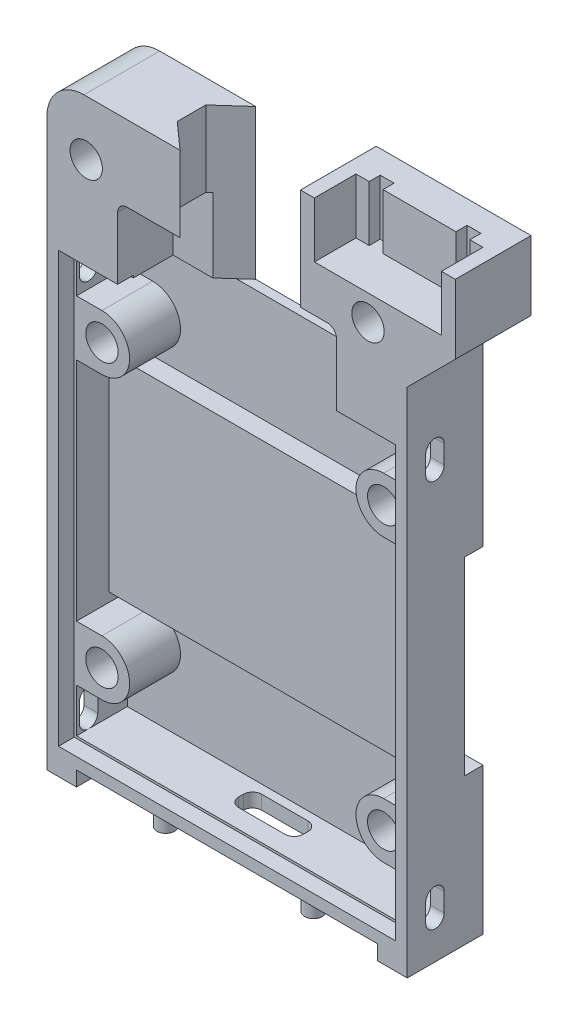
SolidWorks part; units mm, degrees
ref_plane "Front Plane" through (0, 0, 0) normal (0, 0, 1) x (1, 0, 0)
ref_plane "Top Plane" through (0, 0, 0) normal (0, 1, 0) x (1, 0, 0)
ref_plane "Right Plane" through (0, 0, 0) normal (1, 0, 0) x (0, 0, -1)
sketch "Sketch1" plane through (0, 0, 0) normal (0, 0, 1) x (1, 0, 0)
  line L0 (15.25, -20.35) -> (18, -20.35)
  line L1 (-19.5, -32.6) -> (19.5, -32.6)
  line L2 (-19.5, -32.6) -> (-19.5, 31.1)
  line L3 (-19.5, 31.1) -> (19.5, 31.1)
  line L4 (19.5, -32.6) -> (19.5, 31.1)
  line L5 (-15.25, -20.35) -> (-18, -20.35)
  line L6 (15.25, -26.35) -> (18, -26.35)
  line L7 (6.95, 31.1) -> (-15.5, 31.1) construction
  line L8 (-18, -31.1) -> (-18, 29.6)
  line L9 (-18, 29.6) -> (18, 29.6)
  line L10 (18, -31.1) -> (18, 29.6)
  line L11 (-18, -31.1) -> (18, -31.1)
  line L12 (-18, 14.9) -> (18, 14.9)
  line L13 (7.85, 14.9) -> (-4.95, 14.9) construction
  line L14 (-15.25, 4.15) -> (-18, 4.15)
  line L15 (-15.25, 10.15) -> (-18, 10.15)
  line L16 (15.25, 10.15) -> (18, 10.15)
  line L17 (15.25, 4.15) -> (18, 4.15)
  line L18 (-15.25, -26.35) -> (-18, -26.35)
  line L19 (19.5, -34.2) -> (19.5, -18.35) construction
  line L20 (-19.5, -34.2) -> (-19.5, -18.35) construction
  line L21 (15.3, -32.6) -> (-15.3, -32.6) construction
  line L22 (0, 31.1) -> (0, -32.6) construction
  line L23 (9.45, 26.9) -> (24.7, 26.9)
  line L24 (9.45, 26.9) -> (9.45, 33.9)
  line L25 (9.45, 33.9) -> (24.7, 33.9)
  line L26 (24.7, 26.9) -> (24.7, 33.9)
  line L27 (18, 29.6) -> (19.5, 31.1) construction
  line L28 (18.75, 30.35) -> (0, 30.35) construction
  line L29 (9.45, 26.9) -> (7.95, 26.9) construction
  line L30 (-7.95, 31.1) -> (7.95, 31.1)
  line L31 (-7.95, 31.1) -> (-7.95, 29.6)
  line L32 (-7.95, 29.6) -> (7.95, 29.6)
  line L33 (7.95, 31.1) -> (7.95, 29.6)
  line L34 (-7.95, 31.1) -> (7.95, 29.6) construction
  line L35 (-7.95, 29.6) -> (7.95, 31.1) construction
  line L36 (7.95, 26.9) -> (7.95, 29.6) construction
  line L37 (18, 29.6) -> (19.5, 29.6) construction
  line L38 (24.7, 26.4) -> (19.5, 21.2)
  line L39 (9.45, 33.9) -> (7.95, 33.9)
  line L40 (23.2, 33.9) -> (23.2, 26.9)
  line L41 (7.95, 33.9) -> (7.95, 31.1)
  line L42 (24.7, 30.4) -> (23.2, 30.4) construction
  line L43 (24.7, 26.9) -> (19.5, 26.9)
  line L44 (24.7, 26.9) -> (24.7, 26.4)
  line L45 (24.7, 26.4) -> (19.5, 26.4)
  line L46 (19.5, 26.9) -> (19.5, 26.4)
  arc A1 (-15.5, 31.1) -> (-19.5, 27.1) centre (-15.5, 27.1) ccw construction
  arc A3 (-15.5, 31.1) -> (-19.5, 27.1) centre (-15.5, 27.1) ccw
  arc A4 (-15.5, 29.6) -> (-18, 27.1) centre (-15.5, 27.1) ccw
  circle A6 centre (-15.25, -23.35) radius 1.75
  circle A7 centre (15.25, -23.35) radius 1.75
  circle A8 centre (-15.25, 7.15) radius 1.75
  circle A9 centre (15.25, 7.15) radius 1.75
  circle A10 centre (15.25, 25.15) radius 1.75
  circle A11 centre (-15.25, 25.15) radius 1.75
  circle A12 centre (-15.25, -23.35) radius 3
  circle A13 centre (15.25, -23.35) radius 3
  circle A14 centre (15.25, 7.15) radius 3
  circle A15 centre (-15.25, 7.15) radius 3
  dimension "D2" = 1.5
  dimension "D4" = 6
  dimension "D3" = 3.5
  dimension "D5" = 13.75
  dimension "D6" = 15.9
  dimension "D7" = 7
  dimension "D8" = 45
  dimension "D9" = 0.5
  dimension "D1" = 1.5
extrude "Base shape" add sketch "Sketch1" along normal up to surface (8.2 mm away) contours L3 A3 L2 L1 L4 A15 L8 L9 L10 A14 A13 L11 A12 | A15 L15 L8 | A15 L8 L14 | A12 L5 L8 | A12 L8 L18 | A13 L10 L0 | A13 L6 L10 | A14 L10 L16 | A14 L17 L10 | L9 A4 L8 L12 L10 A11 A10 | A4 L9 L8 | L10 A13 | L10 A13 A7 | A12 L8 A6 | L8 A12 | A15 L8 A8 | L8 A15 | L10 A14 | L10 A14 A9 | L33 L3 L31 L9 | L3 L33 L9 L24 | L24 L9 L10 L23 L4 L3 | L24 L23 L10 L9 | L23 L26 L25 L24 L3 L4 | L23 L4 | L3 L24 | L25 L40 L23 L26 | L38 L45 L4 region at (16.8481, -20.9099, 0) region at (17.3601, -20.8437, 0) region at (18.7469, -8.1, 0) region at (17.3601, -25.8563, 0) region at (18.1004, -23.35, 0) region at (17.3601, 4.6437, 0) region at (16.8481, 4.7099, 0) region at (18.1004, 7.15, 0) region at (17.3601, 9.6563, 0) region at (-17.3601, -25.8563, 0) region at (-0.6044, 21.831, 0) region at (-18.1004, -23.35, 0) region at (-17.9169, -23.35, 0) region at (13.725, 28.25, 0) region at (15.3803, 29.9053, 0) region at (-17.3601, -20.8437, 0) region at (22.1, 26.65, 0) region at (17.77, 31.4935, 0) region at (-17.3601, 9.6563, 0) region at (-17.4416, 29.0416, 0) region at (8.7, 30.35, 0) region at (21.2333, 24.6667, 0) region at (23.95, 30.4, 0) region at (-16.8481, 9.5901, 0) region at (-18.1004, 7.15, 0) region at (-17.3601, 4.6437, 0) region at (0, 30.35, 0) region at (8.7, 32.5, 0)
sketch "Sketch3" plane through (19.5, 0, 0) normal (1, 0, 0) x (0, 0, -1)
  line L1 (0, -18.35) -> (-2, -18.35)
  line L2 (0, -18.35) -> (0, 2.15)
  line L3 (0, 2.15) -> (-2, 2.15)
  line L4 (-2, -18.35) -> (-2, 2.15)
  line L5 (0, -18.35) -> (2, -18.35) construction
  line L6 (0, 2.15) -> (2, 2.15) construction
  line L7 (0, -32.6) -> (0, 21.2) construction
  dimension "D1" = 2
extrude "Strap cut" cut sketch "Sketch3" against normal through all
sketch "Sketch4" plane through (0, 31.1, 0) normal (0, 1, 0) x (1, 0, 0)
  line L2 (7.95, 0) -> (-5.0998, 0)
  line L4 (-15.5, 0) -> (7.95, 0) construction
  line L5 (-15.5, -8.2) -> (7.95, -8.2) construction
  line L6 (7.95, -8.2) -> (-5.0998, -8.2)
  line L12 (7.95, -8.3) -> (7.95, 0.1)
  line L13 (7.95, 0.1) -> (-4.9883, 0.1)
  line L14 (-4.9883, 0.1) -> (-7.95, -2.5553)
  line L15 (-7.95, -2.5553) -> (-7.95, -5.6447)
  line L16 (-7.95, -5.6447) -> (-4.9883, -8.3)
  line L17 (-4.9883, -8.3) -> (7.95, -8.3)
  line L18 (7.95, -8.3) -> (7.95, 0.1)
  line L19 (7.95, 0.1) -> (-4.9883, 0.1)
  line L20 (-4.9883, 0.1) -> (-7.95, -2.5553)
  line L21 (-7.95, -2.5553) -> (-7.95, -5.6447)
  line L22 (-7.95, -5.6447) -> (-4.9883, -8.3)
  line L23 (-4.9883, -8.3) -> (7.95, -8.3)
  dimension "D1" = 0.1
extrude "XT60 cut" cut sketch "Sketch4" against normal up to next contours L21 L22 L18 L20 region at (0.4142, 31.1, 4.1)
sketch "Sketch5" plane through (19.5, 0, 0) normal (1, 0, 0) x (0, 0, -1)
  line L1 (-8.2, -32.6) -> (-8.2, 21.2) construction
  line L2 (-6.2, -31.1) -> (-4.2, -31.1)
  line L3 (-6.2, -31.1) -> (-6.2, -27.1)
  line L4 (-6.2, -27.1) -> (-4.2, -27.1)
  line L5 (-4.2, -31.1) -> (-4.2, -27.1)
  line L6 (-8.2, -31.1) -> (0, -31.1) construction
  line L7 (-8.2, 14.9) -> (0, 14.9) construction
  line L8 (-6.2, 14.9) -> (-4.2, 14.9)
  line L9 (-6.2, 14.9) -> (-6.2, 10.9)
  line L10 (-6.2, 10.9) -> (-4.2, 10.9)
  line L11 (-4.2, 14.9) -> (-4.2, 10.9)
  line L14 (-5.2, -27.1) -> (-5.2, -31.1) construction
  line L15 (-5.2, 14.9) -> (-5.2, 10.9) construction
  circle A0 centre (-5.2, -28.1) radius 1
  circle A1 centre (-5.2, -30.1) radius 1
  circle A2 centre (-5.2, 13.9) radius 1
  circle A3 centre (-5.2, 11.9) radius 1
  point P20 (-5.2, -29.1)
  point P31 (-5.2, 12.9)
  dimension "D3" = 4
  dimension "D1" = 2
  dimension "D2" = 2
extrude "Power wires cut" cut sketch "Sketch5" against normal through all contours A2 | A3 | A3 A2 L9 | A3 L11 A2 | A1 | A0 | A1 L5 A0 | A1 A0 L3 region at (19.5, -30.1, 5.2) region at (19.5, -29.1, 5.9766) region at (19.5, -29.1, 4.4234) region at (19.5, -28.1, 5.2) region at (19.5, 13.9, 5.2) region at (19.5, 12.9, 5.9766) region at (19.5, 12.9, 4.4234) region at (19.5, 11.9, 5.2)
sketch "Sketch6" plane through (0, 0, 8.2) normal (0, 0, 1) x (1, 0, 0)
  line L0 (-7.85, 15.9) -> (-7.85, 21.9) construction
  line L1 (-8.85, 22.9) -> (-10.85, 22.9) construction
  line L2 (-11.85, 15.9) -> (-11.85, 21.9) construction
  line L3 (-8.85, 14.9) -> (-10.85, 14.9) construction
  line L4 (-7.85, 15.9) -> (-7.85, 21.9)
  line L5 (-8.85, 22.9) -> (-10.85, 22.9)
  line L6 (-11.85, 15.9) -> (-11.85, 21.9)
  line L7 (-8.85, 14.9) -> (-10.85, 14.9)
  line L8 (7.85, 15.9) -> (7.85, 21.9) construction
  line L9 (8.85, 22.9) -> (10.85, 22.9) construction
  line L10 (11.85, 15.9) -> (11.85, 21.9) construction
  line L11 (8.85, 14.9) -> (10.85, 14.9) construction
  line L12 (7.85, 15.9) -> (7.85, 21.9)
  line L13 (8.85, 22.9) -> (10.85, 22.9)
  line L14 (11.85, 15.9) -> (11.85, 21.9)
  line L15 (8.85, 14.9) -> (10.85, 14.9)
  line L17 (-11.85, 15.9) -> (-7.85, 15.9)
  line L18 (-11.85, 15.9) -> (-11.85, 14.9)
  line L19 (-11.85, 14.9) -> (-7.85, 14.9)
  line L20 (-7.85, 15.9) -> (-7.85, 14.9)
  line L22 (11.85, 15.9) -> (7.85, 15.9)
  line L23 (11.85, 15.9) -> (11.85, 14.9)
  line L24 (11.85, 14.9) -> (7.85, 14.9)
  line L25 (7.85, 15.9) -> (7.85, 14.9)
  line L26 (-18, 14.9) -> (-5.0998, 14.9) construction
  line L27 (11.85, 21.9) -> (7.85, 21.9)
  line L28 (11.85, 21.9) -> (11.85, 22.9)
  line L29 (11.85, 22.9) -> (7.85, 22.9)
  line L30 (7.85, 21.9) -> (7.85, 22.9)
  line L31 (-8.85, 22.9) -> (7.95, 22.9)
  line L32 (-8.85, 22.9) -> (-8.85, 14.9)
  line L33 (-8.85, 14.9) -> (7.95, 14.9)
  line L34 (7.95, 22.9) -> (7.95, 14.9)
  line L35 (7.95, 14.9) -> (18, 14.9) construction
  line L36 (7.95, 14.9) -> (7.95, 33.9) construction
  arc A0 (-8.85, 14.9) -> (-7.85, 15.9) centre (-8.85, 15.9) ccw construction
  arc A1 (-7.85, 21.9) -> (-8.85, 22.9) centre (-8.85, 21.9) ccw construction
  arc A2 (-10.85, 22.9) -> (-11.85, 21.9) centre (-10.85, 21.9) ccw construction
  arc A3 (-11.85, 15.9) -> (-10.85, 14.9) centre (-10.85, 15.9) ccw construction
  arc A4 (-8.85, 14.9) -> (-7.85, 15.9) centre (-8.85, 15.9) ccw
  arc A5 (-7.85, 21.9) -> (-8.85, 22.9) centre (-8.85, 21.9) ccw
  arc A6 (-10.85, 22.9) -> (-11.85, 21.9) centre (-10.85, 21.9) ccw
  arc A7 (-11.85, 15.9) -> (-10.85, 14.9) centre (-10.85, 15.9) ccw
  arc A8 (8.85, 22.9) -> (7.85, 21.9) centre (8.85, 21.9) ccw construction
  arc A9 (11.85, 21.9) -> (10.85, 22.9) centre (10.85, 21.9) ccw construction
  arc A10 (10.85, 14.9) -> (11.85, 15.9) centre (10.85, 15.9) ccw construction
  arc A11 (7.85, 15.9) -> (8.85, 14.9) centre (8.85, 15.9) ccw construction
  arc A12 (8.85, 22.9) -> (7.85, 21.9) centre (8.85, 21.9) ccw
  arc A13 (11.85, 21.9) -> (10.85, 22.9) centre (10.85, 21.9) ccw
  arc A14 (10.85, 14.9) -> (11.85, 15.9) centre (10.85, 15.9) ccw
  arc A15 (7.85, 15.9) -> (8.85, 14.9) centre (8.85, 15.9) ccw
  line M1 (7.95, 33.9) -> (7.95, 14.9)
  line M15 (-5.0998, 14.9) -> (-5.0998, 31.1)
extrude "IO wires cut" cut sketch "Sketch6" against normal blind 6 contours L33 L25 L12 L30 L31 M15 | A5 L4 L20 L31 M15 | L4 A5 L32 L17 | L5 A6 L6 L17 L32 | A7 L18 | L17 A7 L32 | L32 A4 L17 | A4 L20 | A12 L29 L30 M1 | L27 L12 L22 M1 | L22 A15 M1 | A15 L25 L24 L34 | A15 L34 | A15 A14 L22 M1 | A14 L23 | L14 L27 L22 M1 | L27 A13 L13 A12 L34 | A12 L29 M1 region at (-8.3587, 19.2964, 8.2) region at (-8.4256, 15.4756, 8.2) region at (-6.4903, 18.9365, 8.2) region at (-8.0734, 15.1234, 8.2) region at (-10.2516, 15.4213, 8.2) region at (-10.3368, 19.3662, 8.2) region at (-11.6266, 15.1234, 8.2) region at (1.3751, 18.9, 8.2) region at (7.8959, 15.2606, 8.2) region at (7.8959, 22.5394, 8.2) region at (8.1604, 15.056, 8.2) region at (7.9, 18.9, 8.2) region at (7.9098, 15.7354, 8.2) region at (8.1604, 22.744, 8.2) region at (9.8661, 15.4307, 8.2) region at (9.9, 18.9, 8.2) region at (9.8661, 22.3693, 8.2) region at (11.6266, 15.1234, 8.2)
sketch "Sketch7" plane through (-18, 0, 0) normal (1, 0, 0) x (0, 0, -1)
  line L6 (0, -18.35) -> (0, -20.35)
  line L7 (-2, -18.35) -> (0, -18.35)
  line L8 (-2, 2.15) -> (-2, -18.35)
  line L9 (0, 2.15) -> (-2, 2.15)
  line L12 (0, 3.15) -> (-3, 3.15)
  line L13 (-3, 3.15) -> (-3, -19.35)
  line L14 (-3, -19.35) -> (-1, -19.35)
  line L15 (-1, -19.35) -> (-1, -20.35)
  line L16 (-1, -20.35) -> (0, -20.35)
  line L17 (0, 3.15) -> (-1, 3.15)
  line L19 (0, -31.1) -> (-1, -31.1)
  line L22 (0, -31.1) -> (0, -20.35)
  line L23 (0, -20.35) -> (-1, -20.35)
  line L24 (-1, -31.1) -> (-1, -20.35)
  line L25 (0, 3.15) -> (0, 14.9)
  line L26 (0, 14.9) -> (-1, 14.9)
  line L27 (-1, 3.15) -> (-1, 14.9)
  line L28 (-5.2, 14.9) -> (0, 14.9) construction
  line L31 (0, -20.35) -> (0, -18.35) construction
  line L32 (0, 2.15) -> (-2, 2.15) construction
  line M48 (0, -20.35) -> (0, -18.35)
  line M49 (0, -18.35) -> (-2, -18.35)
  line M50 (-2, -18.35) -> (-2, 2.15)
  line M51 (-2, 2.15) -> (0, 2.15)
  line M52 (0, 2.15) -> (0, 4.15)
  line M53 (0, 4.15) -> (-8.2, 4.15)
  line M55 (-8.2, -20.35) -> (0, -20.35)
  dimension "D1" = 1
extrude "Bottom" add sketch "Sketch7" along normal up to surface (36 mm away) contours L27 L25 L26 M53 | L27 L12 M52 M53 | L14 L15 L12 L13 M55 M48 M49 M50 M51 M52 | L24 L19 L22 M55 region at (-18, -8.5273, 2.2091) region at (-18, -25.725, 0.5) region at (-18, 3.65, 0.5) region at (-18, 9.525, 0.5) up to face at (18, -8.1, 2.55)
sketch "Sketch9" plane through (0, 0, 0) normal (0, 0, -1) x (-1, 0, 0)
  circle A0 centre (-15.25, -23.35) radius 1.75 construction
  circle A1 centre (-15.25, 7.15) radius 1.75 construction
  circle A2 centre (15.25, 7.15) radius 1.75 construction
  circle A3 centre (15.25, -23.35) radius 1.75 construction
  circle A4 centre (-15.25, -23.35) radius 1.75
  circle A5 centre (-15.25, 7.15) radius 1.75
  circle A6 centre (15.25, 7.15) radius 1.75
  circle A7 centre (15.25, -23.35) radius 1.75
extrude "Bottom holes" cut sketch "Sketch9" against normal up to next
sketch "Sketch8" plane through (0, 0, 8.2) normal (0, 0, 1) x (1, 0, 0)
  line L0 (-6.2152, 14.9) -> (-18, 14.9) construction
  line L1 (-18.25, 15.15) -> (18.25, 15.15)
  line L2 (-18.25, 15.15) -> (-18.25, -31.35)
  line L3 (-18.25, -31.35) -> (18.25, -31.35)
  line L4 (18.25, 15.15) -> (18.25, -31.35)
  line L5 (-18, 14.9) -> (-18.25, 14.9) construction
  line L6 (-18, 14.9) -> (-18, 15.15) construction
  line L7 (18, 14.9) -> (18.25, 14.9) construction
  line L8 (-18, -31.1) -> (-18, -31.35) construction
  dimension "D1" = 0.25
extrude "PCB cut" cut sketch "Sketch8" against normal blind 1.7
sketch "Sketch11" plane through (0, -32.6, 0) normal (0, -1, 0) x (1, 0, 0)
  line L0 (19.5, 8.2) -> (19.5, 0) construction
  line L1 (-19.5, 8.2) -> (19.5, 8.2)
  line L2 (-19.5, 8.2) -> (-19.5, -1.8)
  line L3 (-19.5, -1.8) -> (19.5, -1.8)
  line L4 (19.5, 8.2) -> (19.5, -1.8)
  line L5 (-19.5, 3.2) -> (19.5, 3.2) construction
  line L6 (0, -1.8) -> (0, 8.2) construction
  line L8 (-2.5, 4.45) -> (2.5, 4.45)
  line L9 (-3.5, 3.45) -> (-3.5, 2.95)
  line L10 (-2.5, 1.95) -> (2.5, 1.95)
  line L11 (3.5, 3.45) -> (3.5, 2.95)
  line L12 (-3.5, 4.45) -> (3.5, 1.95) construction
  line L13 (-3.5, 1.95) -> (3.5, 4.45) construction
  arc A0 (2.5, 4.45) -> (3.5, 3.45) centre (2.5, 3.45) cw
  arc A1 (2.5, 1.95) -> (3.5, 2.95) centre (2.5, 2.95) ccw
  arc A2 (-3.5, 2.95) -> (-2.5, 1.95) centre (-2.5, 2.95) ccw
  arc A3 (-2.5, 4.45) -> (-3.5, 3.45) centre (-2.5, 3.45) ccw
  point P11 (0, 3.2)
  dimension "D4" = 1
  dimension "D1" = 10
  dimension "D2" = 7
  dimension "D3" = 2.5
extrude "Ledbar wires cut" cut sketch "Sketch11" against normal up to next contours L8 A3 L9 A2 L10 A1 L11 A0 region at (0, -32.6, 3.2)
sketch "Sketch13" plane through (0, -32.6, 0) normal (0, -1, 0) x (1, 0, 0)
  line L0 (-19.5, 8.2) -> (19.5, 8.2) construction
  line L1 (19.5, 0) -> (16.3, 0)
  line L2 (19.5, 0) -> (19.5, 8.2)
  line L3 (19.5, 8.2) -> (16.3, 8.2)
  line L4 (16.3, 0) -> (16.3, 8.2)
  line L5 (16.1, -1.8) -> (16.1, 8.2) construction
  line L6 (0, 8.2) -> (0, 0) construction
  line L7 (-19.5, 0) -> (-16.3, 0)
  line L8 (-19.5, 0) -> (-19.5, 8.2)
  line L9 (-19.5, 8.2) -> (-16.3, 8.2)
  line L10 (-16.3, 0) -> (-16.3, 8.2)
  dimension "D1" = 0.2
extrude "Ledbar sides" add sketch "Sketch13" along normal blind 1.6
sketch "Sketch14" plane through (0, -32.6, 0) normal (0, -1, 0) x (1, 0, 0)
  circle A0 centre (8, 6.85) radius 0.95
  circle A1 centre (-8, 6.85) radius 0.95
  dimension "D1" = 1.9
extrude "Ledbar mounts" add sketch "Sketch14" along normal blind 1.8
sketch "Sketch16" plane through (0, 33.9, 0) normal (0, 1, 0) x (1, 0, 0)
  line L0 (7.95, -5.95) -> (24.7, -5.95) construction
  line L1 (7.95, -8.2) -> (24.7, -8.2) construction
  line L2 (21.775, -2.5) -> (20.275, -2.5)
  line L3 (20.275, -3.7) -> (20.275, -2.5)
  line L4 (9.45, -3.7) -> (23.2, -3.7)
  line L5 (9.45, -3.7) -> (9.45, -8.2)
  line L6 (9.45, -8.2) -> (23.2, -8.2)
  line L7 (23.2, -3.7) -> (23.2, -8.2)
  line L8 (9.45, -3.7) -> (23.2, -8.2) construction
  line L9 (9.45, -8.2) -> (23.2, -3.7) construction
  line L10 (24.7, -8.2) -> (24.7, 0) construction
  line L11 (7.95, -8.2) -> (7.95, 0) construction
  line L12 (16.325, -8.2) -> (16.325, -3.7) construction
  line L13 (11.625, -2.5) -> (11.625, -3.7) construction
  line L14 (10.875, -3.7) -> (12.375, -3.7)
  line L15 (10.875, -3.7) -> (10.875, -2.5)
  line L16 (10.875, -2.5) -> (12.375, -2.5)
  line L17 (12.375, -3.7) -> (12.375, -2.5)
  line L18 (10.875, -2.5) -> (10.875, -8.2) construction
  line L19 (21.775, -3.7) -> (21.775, -2.5)
  point P6 (16.325, -5.95)
  dimension "D1" = 13.75
  dimension "D2" = 4.5
  dimension "D3" = 1.5
  dimension "D4" = 1.2
  dimension "D5" = 4.7
extrude "Balance plug cut" cut sketch "Sketch16" against normal blind 6 contours L7 L4 L5 L6 | L4 L17 L16 L15 | L4 L19 L2 L3 region at (21.025, 33.9, 3.1) region at (16.325, 33.9, 5.95) region at (11.625, 33.9, 3.1)
sketch "Sketch10" [suppressed] plane through (0, 0, 2) normal (0, 0, -1) x (-1, 0, 0)
  line L0 (0, 2.15) -> (0, -18.35) construction
  line L1 (19.5, 2.15) -> (-19.5, 2.15) construction
  line L2 (19.5, -18.35) -> (-19.5, -18.35) construction
  line L3 (19.5, 2.15) -> (19.5, -18.35) construction
  line L4 (-19.5, 1.15) -> (19.5, 1.15)
  line L5 (-19.5, 1.15) -> (-19.5, 0.65)
  line L6 (-19.5, 0.65) -> (19.5, 0.65)
  line L7 (19.5, 1.15) -> (19.5, 0.65)
  line L8 (-19.5, 1.15) -> (19.5, 0.65) construction
  line L9 (-19.5, 0.65) -> (19.5, 1.15) construction
  line L10 (-19.5, 2.15) -> (19.5, 2.15) construction
  line L11 (-19.5, -1.35) -> (19.5, -1.35)
  line L12 (19.5, -0.85) -> (19.5, -1.35)
  line L13 (-19.5, -0.85) -> (19.5, -0.85)
  line L14 (-19.5, -0.85) -> (-19.5, -1.35)
  line L15 (-19.5, -3.35) -> (19.5, -3.35)
  line L16 (19.5, -2.85) -> (19.5, -3.35)
  line L17 (-19.5, -2.85) -> (19.5, -2.85)
  line L18 (-19.5, -2.85) -> (-19.5, -3.35)
  line L19 (-19.5, -5.35) -> (19.5, -5.35)
  line L20 (19.5, -4.85) -> (19.5, -5.35)
  line L21 (-19.5, -4.85) -> (19.5, -4.85)
  line L22 (-19.5, -4.85) -> (-19.5, -5.35)
  line L23 (-19.5, -7.35) -> (19.5, -7.35)
  line L24 (19.5, -6.85) -> (19.5, -7.35)
  line L25 (-19.5, -6.85) -> (19.5, -6.85)
  line L26 (-19.5, -6.85) -> (-19.5, -7.35)
  line L27 (-19.5, -9.35) -> (19.5, -9.35)
  line L28 (19.5, -8.85) -> (19.5, -9.35)
  line L29 (-19.5, -8.85) -> (19.5, -8.85)
  line L30 (-19.5, -8.85) -> (-19.5, -9.35)
  line L31 (-19.5, -11.35) -> (19.5, -11.35)
  line L32 (19.5, -10.85) -> (19.5, -11.35)
  line L33 (-19.5, -10.85) -> (19.5, -10.85)
  line L34 (-19.5, -10.85) -> (-19.5, -11.35)
  line L35 (-19.5, -13.35) -> (19.5, -13.35)
  line L36 (19.5, -12.85) -> (19.5, -13.35)
  line L37 (-19.5, -12.85) -> (19.5, -12.85)
  line L38 (-19.5, -12.85) -> (-19.5, -13.35)
  line L39 (-19.5, -15.35) -> (19.5, -15.35)
  line L40 (19.5, -14.85) -> (19.5, -15.35)
  line L41 (-19.5, -14.85) -> (19.5, -14.85)
  line L42 (-19.5, -14.85) -> (-19.5, -15.35)
  line L43 (-19.5, -17.35) -> (19.5, -17.35)
  line L44 (19.5, -16.85) -> (19.5, -17.35)
  line L45 (-19.5, -16.85) -> (19.5, -16.85)
  line L46 (-19.5, -16.85) -> (-19.5, -17.35)
  point P6 (0, 0.9)
  dimension "D1" = 1
  dimension "D2" = 0.5
  dimension "D4" = 2
  dimension "D3" = 10
extrude "3D print ribs" [suppressed] add sketch "Sketch10" along normal up to surface (2 mm away) up to face at (13.5, 7.15, 0)
sketch "Sketch15" [suppressed] plane through (0, 0, 0) normal (0, 0, -1) x (-1, 0, 0)
  line L0 (-8, -34.4) -> (-8, -32.6) construction
  line L1 (-8.95, -34.4) -> (-7.05, -34.4) construction
  line L2 (-8.95, -32.6) -> (-7.05, -32.6) construction
  line L3 (0, -32.6) -> (0, 14.9) construction
  line L4 (-8.25, -34.4) -> (-7.75, -34.4)
  line L5 (-8.25, -34.4) -> (-8.25, -32.6)
  line L6 (-8.25, -32.6) -> (-7.75, -32.6)
  line L7 (-7.75, -34.4) -> (-7.75, -32.6)
  line L8 (-8.25, -34.4) -> (-7.75, -32.6) construction
  line L9 (-8.25, -32.6) -> (-7.75, -34.4) construction
  line L10 (16.3, -32.6) -> (-16.3, -32.6) construction
  line L11 (-7.95, 14.9) -> (5.0998, 14.9) construction
  line L12 (8.25, -32.6) -> (7.75, -32.6)
  line L13 (7.75, -34.4) -> (7.75, -32.6)
  line L14 (8.25, -34.4) -> (7.75, -34.4)
  line L15 (8.25, -34.4) -> (8.25, -32.6)
  point P6 (-8, -33.5)
  dimension "D1" = 0.5
extrude "3D print led supports" [suppressed] add sketch "Sketch15" against normal up to next
